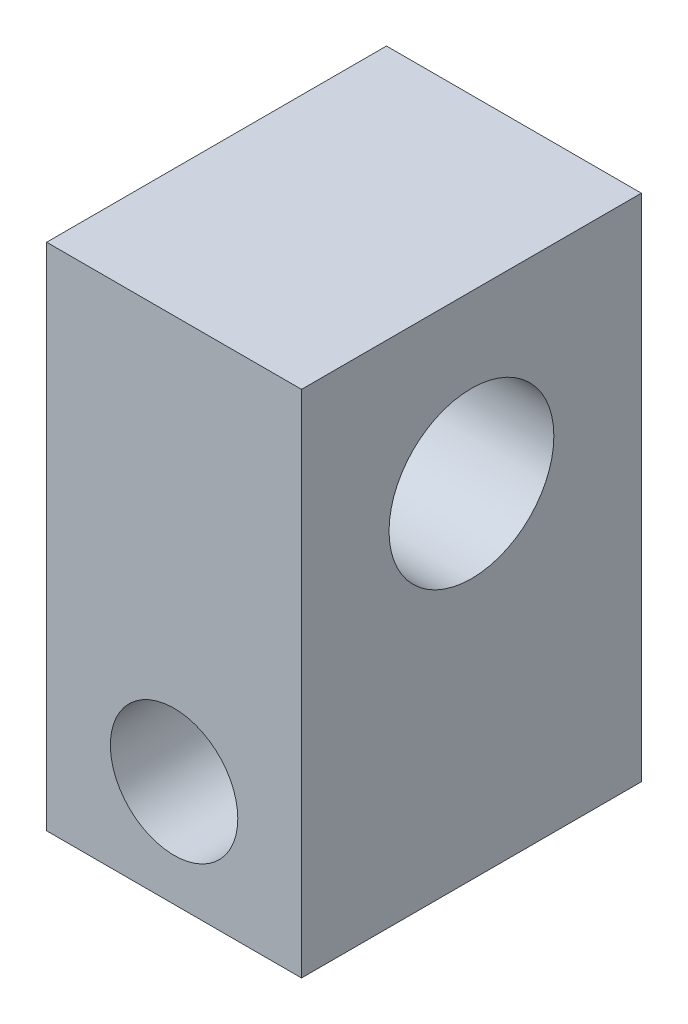
SolidWorks part; units mm, degrees
ref_plane "Front Plane" through (0, 0, 0) normal (0, 0, 1) x (1, 0, 0)
ref_plane "Top Plane" through (0, 0, 0) normal (0, 1, 0) x (1, 0, 0)
ref_plane "Right Plane" through (0, 0, 0) normal (1, 0, 0) x (0, 0, -1)
sketch "Sketch1" plane through (0, 0, 0) normal (0, 1, 0) x (1, 0, 0)
  line L1 (-9.525, -12.7) -> (9.525, -12.7)
  line L2 (-9.525, -12.7) -> (-9.525, 12.7)
  line L3 (-9.525, 12.7) -> (9.525, 12.7)
  line L4 (9.525, -12.7) -> (9.525, 12.7)
  line L5 (-9.525, -12.7) -> (9.525, 12.7) construction
  line L6 (-9.525, 12.7) -> (9.525, -12.7) construction
  point P0 (0, 0)
  dimension "D1" = 19.05
  dimension "D2" = 25.4
extrude "Boss-Extrude1" add sketch "Sketch1" along normal blind 38.1
sketch "Sketch2" plane through (0, 0, 12.7) normal (0, 0, 1) x (1, 0, 0)
  circle A0 centre (0, 7.9375) radius 4.7625
  dimension "D1" = 9.525
  dimension "D2" = 7.9375
extrude "Cut-Extrude1" cut sketch "Sketch2" against normal through all
sketch "Sketch3" plane through (9.525, 0, 0) normal (1, 0, 0) x (0, 0, -1)
  line L0 (-12.7, 38.1) -> (12.7, 38.1) construction
  circle A0 centre (0, 25.654) radius 6.1595
  dimension "D1" = 12.319
  dimension "D2" = 12.446
extrude "Cut-Extrude2" cut sketch "Sketch3" against normal through all
